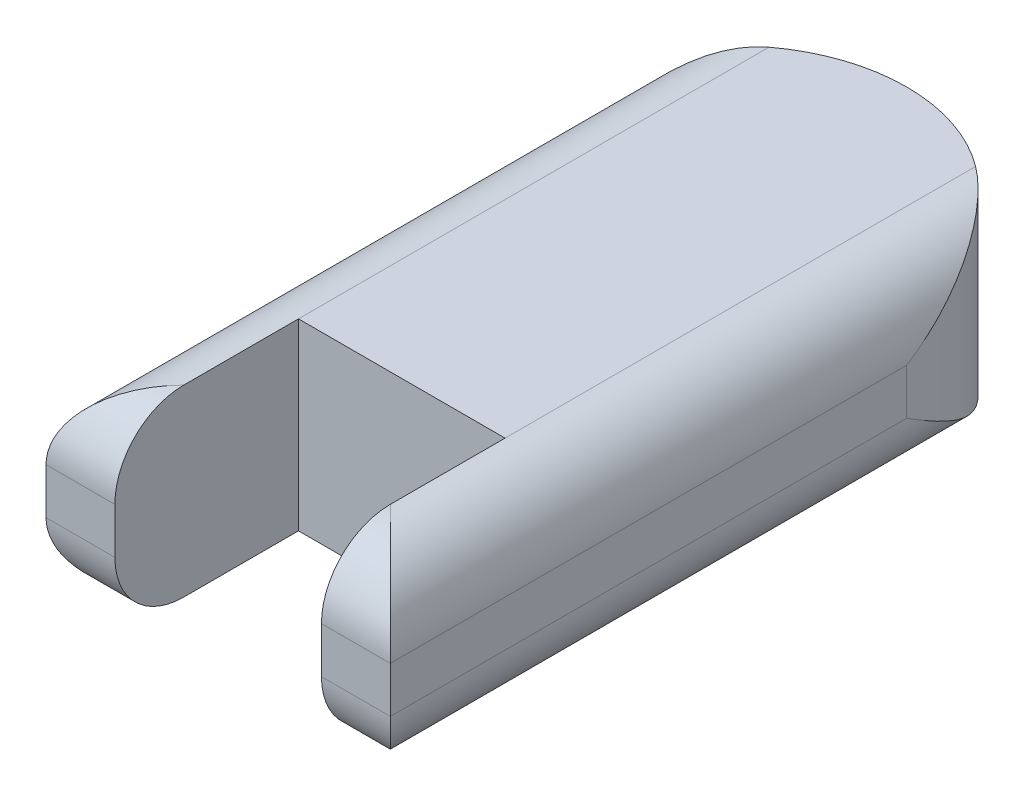
SolidWorks part; units mm, degrees
ref_plane "Alzado" through (0, 0, 0) normal (0, 0, 1) x (1, 0, 0)
ref_plane "Planta" through (0, 0, 0) normal (0, 1, 0) x (1, 0, 0)
ref_plane "Vista lateral" through (0, 0, 0) normal (1, 0, 0) x (0, 0, -1)
sketch "Sketch1" plane through (0, 0, 0) normal (0, 0, 1) x (1, 0, 0)
  line L1 (-45, -40) -> (45, -40)
  line L2 (-75, -10) -> (-75, 10)
  line L3 (-45, 40) -> (45, 40)
  line L4 (75, -10) -> (75, 10)
  line L5 (-75, -40) -> (75, 40) construction
  line L6 (-75, 40) -> (75, -40) construction
  arc A0 (-75, 10) -> (-45, 40) centre (-45, 10) cw
  arc A1 (45, -40) -> (75, -10) centre (45, -10) ccw
  arc A2 (-45, -40) -> (-75, -10) centre (-45, -10) cw
  arc A3 (45, 40) -> (75, 10) centre (45, 10) cw
  point P0 (0, 0)
  point P8 (24.4311, 4.9627)
  dimension "D3" = 30
  dimension "D4" = 30
  dimension "D1" = 150
  dimension "D2" = 80
extrude "Boss-Extrude1" add sketch "Sketch1" along normal blind 150 and the other way blind 150
sketch "Sketch2" plane through (75, 0, 0) normal (1, 0, 0) x (0, 0, -1)
  line L1 (150, 40) -> (-120, 40)
  line L2 (150, 40) -> (150, -40)
  line L3 (150, -40) -> (-120, -40)
  line L4 (-150, 10) -> (-150, -10)
  arc A0 (-120, -40) -> (-150, -10) centre (-120, -10) cw
  arc A1 (-120, 40) -> (-150, 10) centre (-120, 10) ccw
  point P8 (-150, -40)
  dimension "D1" = 30
extrude "Cut-Extrude1" cut sketch "Sketch2" against normal blind 150 flip side to cut
sketch "Sketch3" plane through (0, -40, 0) normal (0, -1, 0) x (1, 0, 0)
  line L1 (-45, 150) -> (45, 150)
  line L2 (-45, 150) -> (-45, 70)
  line L3 (-45, 70) -> (45, 70)
  line L4 (45, 150) -> (45, 70)
  line L5 (-75, 150) -> (75, 150) construction
  line L6 (-45, 120) -> (-45, -150) construction
  line L7 (45, 120) -> (45, -150) construction
  point P5 (-75, 150)
  point P6 (-45.5757, 125.2223)
  point P7 (75, 110)
  point P8 (35.0336, 98.9872)
  point P9 (-34.9971, 135.3778)
  dimension "D1" = 80
extrude "Cut-Extrude2" cut sketch "Sketch3" against normal up to next
sketch "Sketch4" plane through (-45, 0, 0) normal (1, 0, 0) x (0, 0, -1)
  line L0 (-70, 0) -> (-150, 0) construction
  line L1 (-70, 40) -> (-70, -40) construction
  line L3 (-110, -10) -> (-110, -39.4509) construction
  point P3 (-70, 0)
  point P4 (-110, 0)
  point P5 (-110, -27.0119)
  point P8 (0, 0)
  dimension "D1" = 40
ref_axis "Axis2" through (-45, 0, 110) along (1, 0, 0)
sketch "Sketch6" plane through (0, 40, 0) normal (0, 1, 0) x (1, 0, 0)
  line L0 (-75, 75) -> (-75, 0)
  line L5 (-75, 150) -> (-75, -150) construction
  line L7 (75, 150) -> (75, -150) construction
  line L8 (75, 0) -> (75, 75)
  line L9 (45, 150) -> (-45, 150) construction
  line L12 (-75, 0) -> (-75, -150)
  line L13 (-75, -150) -> (75, -150)
  line L14 (75, 0) -> (75, -150)
  arc A0 (-75, 75) -> (75, 75) centre (0, 75) cw
  dimension "D1" = 75
extrude "Cut-Extrude3" cut sketch "Sketch6" against normal through all flip side to cut
sketch "Sketch7" plane through (0, 40, 0) normal (0, 1, 0) x (1, 0, 0)
  point P0 (0, 75)
  point P1 (0, 0)
  point P2 (0, 75)
  point P3 (0, 0)
  point P5 (0, 0)
  point P6 (0, 0)
  point P7 (0, 75)
  point P8 (0, 0)
  dimension "D1" = 75
ref_axis "Axis1" through (0, 40, -75) along (0, 1, 0)
